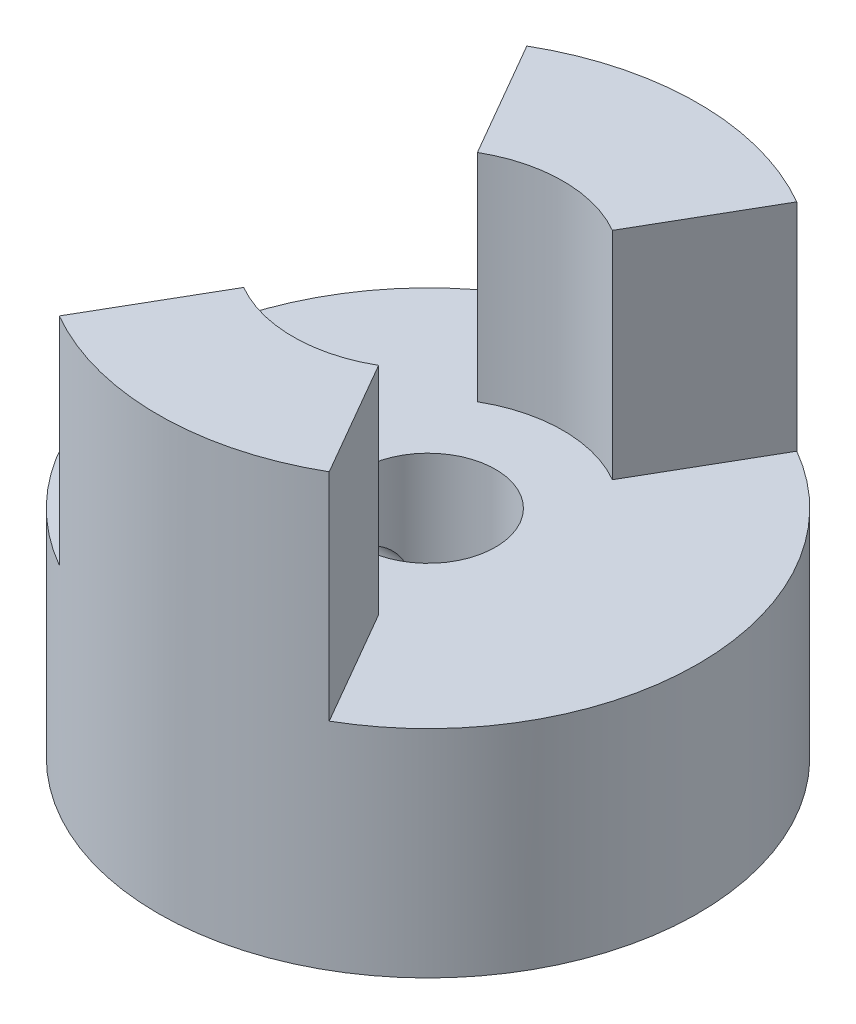
SolidWorks part; units mm, degrees
material "6061 Alloy"
ref_plane "Front Plane" through (0, 0, 0) normal (0, 0, 1) x (1, 0, 0)
ref_plane "Top Plane" through (0, 0, 0) normal (0, 1, 0) x (1, 0, 0)
ref_plane "Right Plane" through (0, 0, 0) normal (1, 0, 0) x (0, 0, -1)
sketch "Sketch1" plane through (0, 0, 0) normal (0, 1, 0) x (1, 0, 0)
  circle A0 centre (0, 0) radius 6.35
extrude "Boss-Extrude1" add sketch "Sketch1" along normal blind 10.16
hole_wizard "1/8 (0.125) Diameter Hole1" positions "Sketch2" profile "Sketch3" hole size "1/8" standard "ANSI Inch" end condition through all
sketch "Sketch2" plane through (0, 10.16, 0) normal (0, 1, 0) x (1, 0, 0)
  point P0 (0, 0)
sketch "Sketch3" plane through (0, 10.16, 0) normal (1, 0, 0) x (0, 0, 1)
  line L0 (0, 0) -> (0, 10.16)
  line L1 (0, 10.16) -> (1.5875, 10.16)
  line L2 (1.5875, 10.16) -> (1.5875, 0)
  line L5 (1.5875, 0) -> (0, 0)
  line L11 (0, -6.35) -> (0, 107.95) construction
  dimension "Thru Hole Dia." = 3.175
  dimension "Thru Hole Depth" = 10.16
sketch "Sketch4" plane through (0, 10.16, 0) normal (0, 1, 0) x (1, 0, 0)
  circle A0 centre (0, 0) radius 3.175
extrude "Cut-Extrude1" cut sketch "Sketch4" against normal blind 5.08
sketch "Sketch5" plane through (0, 10.16, 0) normal (0, 1, 0) x (1, 0, 0)
  line L0 (0, 0) -> (-7.62, -13.1982)
  line L1 (-7.62, -13.1982) -> (-7.62, 13.1982)
  line L2 (-7.62, 13.1982) -> (0, 0)
  line L3 (0, -55) -> (0, 55) construction
  dimension "D4" = 0
  dimension "D1" = 120
  dimension "D2" = 15.24
  dimension "D3" = 15.24
extrude "Cut-Extrude2" cut sketch "Sketch5" against normal blind 5.08
mirror "Mirror1" about plane through (0, 0, 0) normal (1, 0, 0) of "Cut-Extrude2"
hole_wizard "#2-56 Tapped Hole1" positions "3DSketch1" profile "Sketch6" tap size "#2-56" standard "ANSI Inch" end condition up to next
sketch3d "3DSketch1"
  point P0 (-6.35, 2.54, 0.0133)
  dimension "D1" = 2.54
sketch "Sketch6" plane through (-6.35, 2.54, 0.0133) normal (0, 1, 0) x (0.0021, 0, 1)
  line L0 (0, 0) -> (0, 4.7625)
  line L1 (0, 4.7625) -> (0.889, 4.7625)
  line L2 (0.889, 4.7625) -> (0.889, 0)
  line L5 (0.889, 0) -> (0, 0)
  line L11 (0, -6.35) -> (0, 107.95) construction
  dimension "Thru Tap Drill Dia." = 1.778
  dimension "Thru Tap Drill Depth" = 4.7625
cosmetic thread "Hole Thread1" parameters "D2"=2.1844
